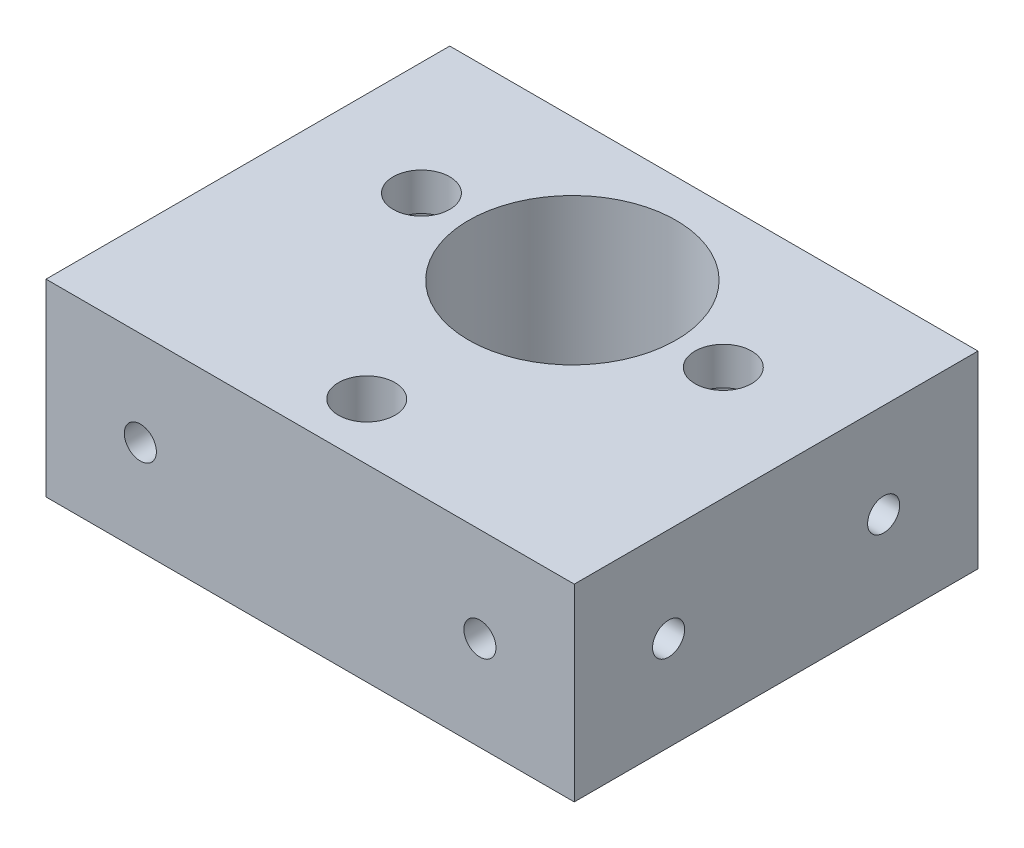
SolidWorks part; units mm, degrees
ref_plane "前视基准面" through (0, 0, 0) normal (0, 0, 1) x (1, 0, 0)
ref_plane "上视基准面" through (0, 0, 0) normal (0, 1, 0) x (1, 0, 0)
ref_plane "右视基准面" through (0, 0, 0) normal (1, 0, 0) x (0, 0, -1)
other "Configuration Table"
sketch "草图1" plane through (0, 0, 0) normal (0, 1, 0) x (1, 0, 0)
  line L0 (-8, 0) -> (8, 0)
  line L33 (-14, -7.5) -> (14, -7.5)
  line L34 (-14, -7.5) -> (-14, 7.5)
  line L35 (-14, 7.5) -> (14, 7.5)
  line L36 (14, -7.5) -> (14, 7.5)
  line L37 (-14, -7.5) -> (14, 7.5) construction
  line L38 (-14, 7.5) -> (14, -7.5) construction
  line L44 (14, -7.5) -> (-14, -7.5)
  line L45 (14, -7.5) -> (14, -13.9)
  line L46 (14, -13.9) -> (-14, -13.9)
  line L47 (-14, -7.5) -> (-14, -13.9)
  circle A0 centre (0, 0) radius 5.5
  circle A1 centre (-8, 0) radius 2.25
  circle A2 centre (-8, 0) radius 1.5
  circle A3 centre (8, 0) radius 2.25
  circle A4 centre (8, 0) radius 1.5
  circle A5 centre (0, -10.9) radius 1.5
  circle A6 centre (0, -10.9) radius 2.25
  point P0 (-90.6464, 22.0667)
  point P11 (0, 0)
  dimension "D1" = 11
  dimension "D2" = 15
  dimension "D3" = 16
  dimension "D4" = 3
  dimension "D5" = 4.5
  dimension "D6" = 28
  dimension "D7" = 13.9
extrude "凸台-拉伸1" add sketch "草图1" along normal blind 10 contours L33 L36 L35 L34 A3 A0 A1 | L33 L47 L46 L45 A6 | A4 A3 | A2 A1 | A6 A5 | L47 L34 region at (-10.1864, 0, 0) region at (8, 0, -2.1864) region at (-13.6824, 0, 0) region at (0, 0, 7.7872) region at (-2.1864, 0, 10.9)
extrude "切除-拉伸5" cut sketch "草图1<17>" along normal offset from surface (8 mm away) 2 contours A3 | A1 up to face at (0, 10, 5.5)
sketch "草图1<17>" plane through (0, 0, 0) normal (0, 1, 0) x (1, 0, 0) same geometry as "草图1"
sketch "草图2" plane through (0, 0, 0) normal (1, 0, 0) x (0, 0, -1)
  line L0 (-13.9, 10) -> (-13.9, 0) construction
  line L1 (7.5, 10) -> (7.5, 0) construction
  circle A0 centre (-8.9, 5) radius 0.85
  circle A1 centre (2.5, 5) radius 0.85
  point P7 (-13.9, 5)
  dimension "D1" = 1.7
  dimension "D2" = 5
  dimension "D3" = 5
extrude "切除-拉伸1" cut sketch "草图2" against normal blind 4 from surface starting at face at (14, 5, 3.2)
extrude "切除-拉伸2" cut sketch "草图2<2>" along normal blind 4 from surface starting at face at (-14, 5, 3.2)
sketch "草图2<2>" plane through (0, 0, 0) normal (1, 0, 0) x (0, 0, -1) same geometry as "草图2"
sketch "草图3" plane through (0, 0, 0) normal (0, 0, 1) x (1, 0, 0)
  line L0 (14, 10) -> (14, 0) construction
  line L1 (-14, 10) -> (-14, 0) construction
  circle A0 centre (-9, 5) radius 0.85
  circle A1 centre (9, 5) radius 0.85
  point P7 (14, 5)
  dimension "D3" = 1.7
  dimension "D1" = 5
  dimension "D2" = 5
extrude "切除-拉伸3" cut sketch "草图3" against normal blind 4 from surface starting at face at (0, 5, 13.9)
extrude "切除-拉伸4" cut sketch "草图3<2>" along normal blind 4 from surface starting at face at (0, 5, -7.5)
sketch "草图3<2>" plane through (0, 0, 0) normal (0, 0, 1) x (1, 0, 0) same geometry as "草图3"
